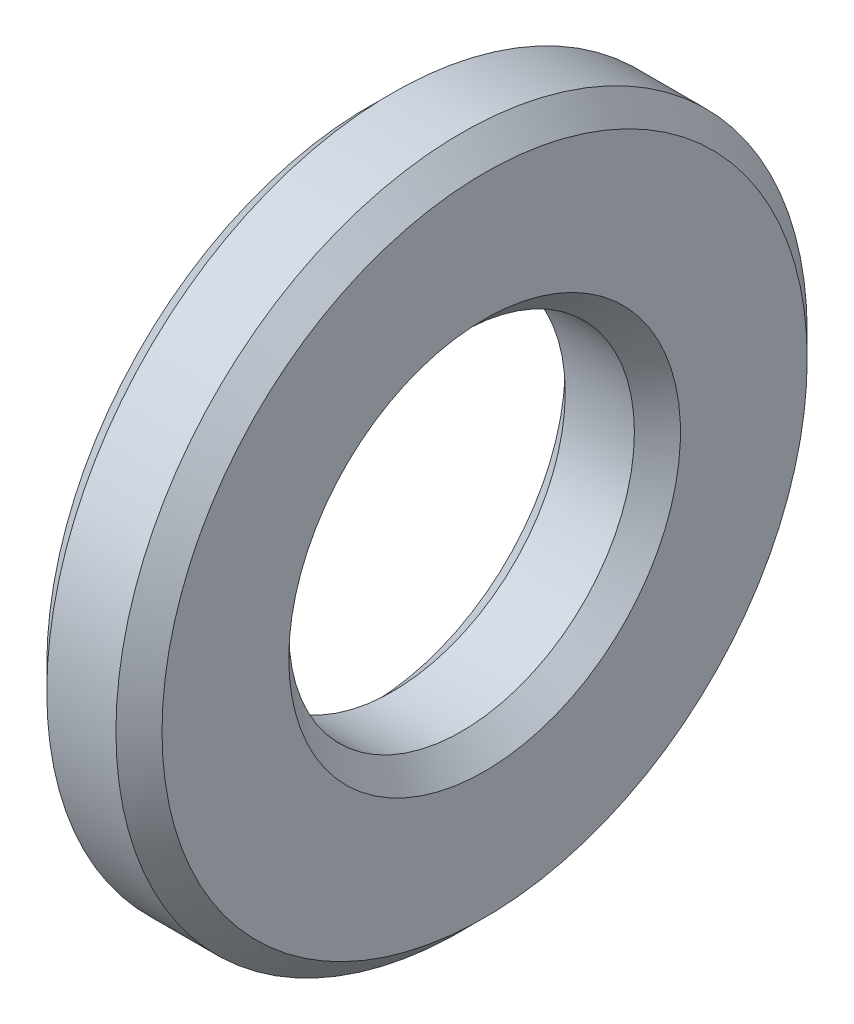
SolidWorks part; units mm, degrees
material "低碳型易切削钢"
ref_plane "Front Plane" through (0, 0, 0) normal (0, 0, 1) x (1, 0, 0)
ref_plane "Top Plane" through (0, 0, 0) normal (0, 1, 0) x (1, 0, 0)
ref_plane "Right Plane" through (0, 0, 0) normal (1, 0, 0) x (0, 0, -1)
ref_axis "Axis_X" through (-0.05, 0, 0) along (1, 0, 0)
ref_axis "Axis_Y" through (0, 3.3, 0) along (0, -1, 0)
ref_axis "Axis_Z" through (0, 0, -3.3) along (0, 0, 1)
sketch "Sketch1" plane through (0, 0, 0) normal (0, 0, 1) x (1, 0, 0)
  line L0 (0, 0) -> (1, 0) construction
  line L1 (0.2, 3) -> (0.8, 3)
  line L2 (0, 2.8) -> (0, 1.7)
  line L3 (0.2, 1.5) -> (0.8, 1.5)
  line L4 (1, 2.8) -> (1, 1.7)
  line L5 (0, 3) -> (1, 1.5) construction
  line L6 (0, 1.5) -> (1, 3) construction
  line L7 (0.2, 3) -> (0, 2.8)
  line L8 (0.8, 3) -> (1, 2.8)
  line L9 (1, 1.7) -> (0.8, 1.5)
  line L10 (0, 1.7) -> (0.2, 1.5)
  line L11 (0, 2.8) -> (0, 3) construction
  line L12 (0, 3) -> (0.2, 3) construction
  line L13 (0.8, 3) -> (1, 3) construction
  line L14 (1, 3) -> (1, 2.8) construction
  line L15 (0.8, 1.5) -> (1, 1.5) construction
  line L16 (1, 1.5) -> (1, 1.7) construction
  line L17 (0, 1.7) -> (0, 1.5) construction
  line L18 (0, 1.5) -> (0.2, 1.5) construction
  point P0 (0.5, 2.25)
  dimension "V" = 3
  dimension "D" = 6
  dimension "T" = 1
  dimension "MSM_1" = 0.2
revolve "Revolve1" add sketch "Sketch1" angle 360 about axis through (-0.05, 0, 0) along (1, 0, 0)
equation "\"Factor\"= 1.082532"
